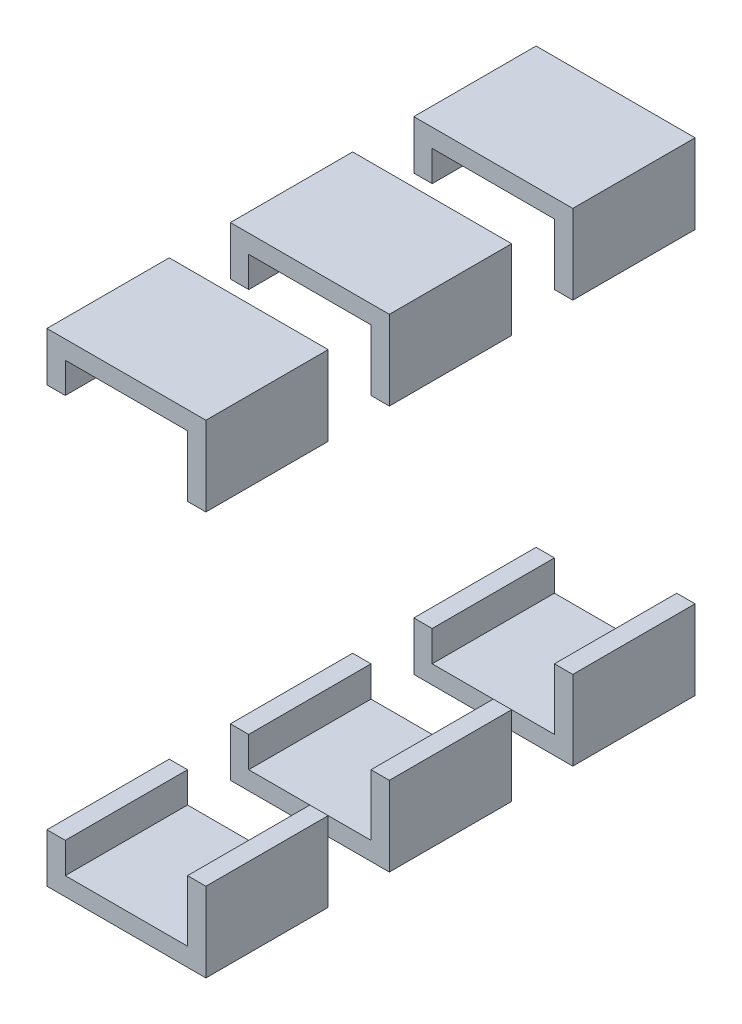
SolidWorks part; units mm, degrees
ref_plane "前视基准面" through (0, 0, 0) normal (0, 0, 1) x (1, 0, 0)
ref_plane "上视基准面" through (0, 0, 0) normal (0, 1, 0) x (1, 0, 0)
ref_plane "右视基准面" through (0, 0, 0) normal (1, 0, 0) x (0, 0, -1)
other "Configuration Table"
sketch "草图1" plane through (0, 0, 0) normal (0, 0, 1) x (1, 0, 0)
  line L9 (-8.64, -35.5) -> (-8.64, -39.5)
  line L10 (17.36, 39.5) -> (-8.64, 39.5)
  line L15 (55, 0) -> (-55, 0) construction
  line L22 (17.36, 39.5) -> (17.36, -39.5)
  line L23 (17.36, -39.5) -> (-8.64, -39.5)
  line L24 (-8.64, 39.5) -> (-8.64, 35.5)
  line L25 (14.36, 36.5) -> (-5.64, 36.5)
  line L26 (14.36, 36.5) -> (14.36, -36.5)
  line L27 (14.36, -36.5) -> (-5.64, -36.5)
  line L28 (-8.64, 35.5) -> (-8.64, 31.5)
  line L29 (-8.64, 31.5) -> (-5.64, 31.5)
  line L30 (-5.64, 36.5) -> (-5.64, 31.5)
  line L31 (-8.64, -31.5) -> (-5.64, -31.5)
  line L32 (-5.64, -36.5) -> (-5.64, -31.5)
  line L34 (-8.64, -35.5) -> (-8.64, -31.5)
  point P0 (0, 0)
  point P7 (0, 0)
  dimension "D1" = 79
  dimension "D2" = 3
  dimension "D3" = 3
  dimension "D4" = 3
  dimension "D5" = 26
  dimension "D6" = 63
  dimension "D7" = 3
extrude "凸台-拉伸1" add sketch "草图1" along normal blind 160
sketch "草图4" plane through (14.36, 0, 0) normal (-1, 0, 0) x (0, 0, 1)
  line L0 (160, -31.5) -> (0, -31.5) construction
  line L1 (140, 26.5) -> (160, 26.5)
  line L3 (140, -26.5) -> (160, -26.5)
  line L4 (160, 26.5) -> (160, -26.5)
  line L5 (140, 26.5) -> (160, -26.5) construction
  line L6 (140, -26.5) -> (160, 26.5) construction
  line L7 (160, 36.5) -> (160, -36.5) construction
  line L12 (140, 26.5) -> (140, 45.304)
  line L13 (100, -45.304) -> (110, -45.304)
  line L14 (110, -45.304) -> (110, -26.5)
  line L15 (110, -26.5) -> (130, -26.5)
  line L16 (130, -45.304) -> (140, -45.304)
  line L17 (140, -45.304) -> (140, -26.5)
  line L18 (140, 45.304) -> (130, 45.304)
  line L19 (130, 45.304) -> (130, 26.5)
  line L21 (110, 26.5) -> (130, 26.5)
  line L22 (110, 26.5) -> (110, 45.304)
  line L23 (110, 45.304) -> (100, 45.304)
  line L30 (100, 45.304) -> (100, 26.5)
  line L31 (72.3419, -45.304) -> (80, -45.304)
  line L34 (80, -45.304) -> (80, -26.5)
  line L35 (80, -26.5) -> (100, -26.5)
  line L39 (80, 26.5) -> (100, 26.5)
  line L42 (80, 26.5) -> (80, 45.304)
  line L43 (80, 45.304) -> (72.3419, 45.304)
  line L45 (100, -26.5) -> (100, -45.304)
  line L46 (130, -26.5) -> (130, -45.304)
  line L47 (72.3419, 45.304) -> (72.3419, 47.203)
  line L48 (-21.5766, -47.2023) -> (72.3419, -47.2023)
  line L49 (72.3419, -47.2023) -> (72.3419, -45.304)
  line L50 (72.3419, 47.203) -> (-21.5766, 47.203)
  line L51 (-21.5766, 47.203) -> (-21.5766, -47.2023)
  line L66 (100, 26.5) -> (100, -26.5) [skipped]
  line L67 (130, 26.5) -> (130, -26.5) [skipped]
  line L68 (70, 45.304) -> (70, -45.304) [skipped]
  point P10 (150, 0)
  dimension "D1" = 53
  dimension "D2" = 5
  dimension "D3" = 10
  dimension "D4" = 20
extrude "切除-拉伸2" cut sketch "草图4" against normal through all and the other way through all
